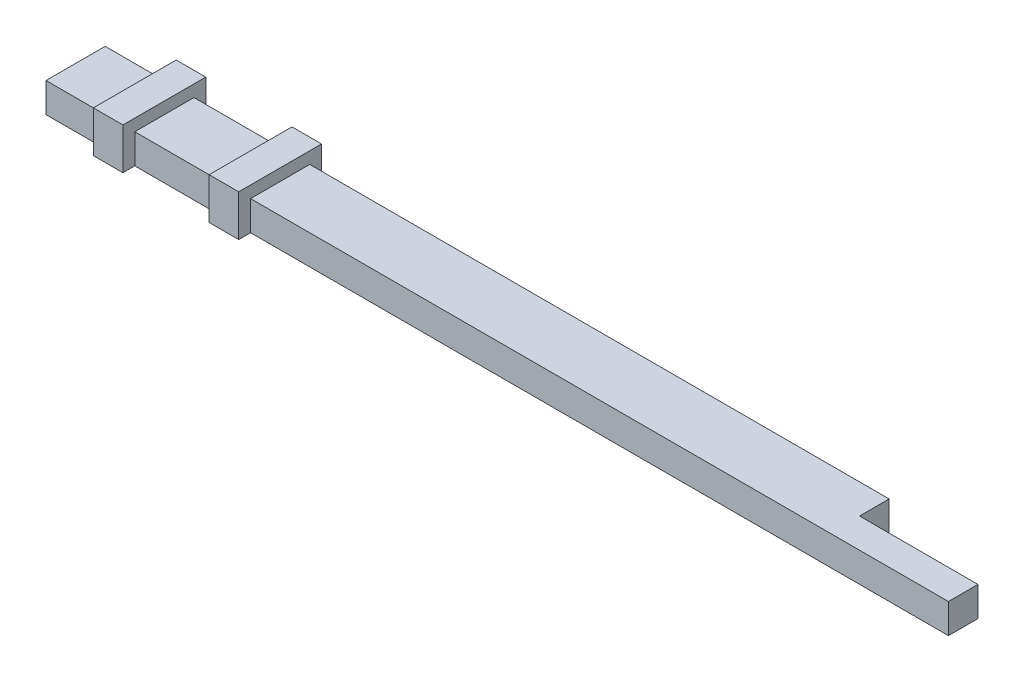
SolidWorks part; units mm, degrees
ref_plane "Front Plane" through (0, 0, 0) normal (0, 0, 1) x (1, 0, 0)
ref_plane "Top Plane" through (0, 0, 0) normal (0, 1, 0) x (1, 0, 0)
ref_plane "Right Plane" through (0, 0, 0) normal (1, 0, 0) x (0, 0, -1)
sketch "Sketch1" plane through (0, 0, 0) normal (0, 1, 0) x (1, 0, 0)
  line L0 (132.4815, 10) -> (132.4815, 5)
  line L1 (0, 0) -> (142.5, 0)
  line L2 (0, 0) -> (0, 10)
  line L3 (0, 10) -> (132.4815, 10)
  line L5 (142.5, 0) -> (152.5, 0)
  line L7 (142.4815, 5) -> (152.5, 5)
  line L8 (152.5, 0) -> (152.5, 5)
  line L9 (132.4815, 5) -> (142.4815, 5)
  dimension "D1" = 142.5
  dimension "D2" = 10
  dimension "D3" = 10
  dimension "D4" = 10
extrude "Boss-Extrude1" add sketch "Sketch1" along normal blind 5
ref_plane "Plane1" through (10, 0, 0) normal (-1, 0, 0) x (0, 0, 1)
sketch "Sketch2" plane through (10, 0, 0) normal (-1, 0, 0) x (0, 0, 1)
  line L0 (-10, 5) -> (0, 5) construction
  line L1 (-12, 7) -> (2, 7)
  line L2 (-12, 7) -> (-12, 0)
  line L3 (-12, 0) -> (2, 0)
  line L4 (2, 7) -> (2, 0)
  line L5 (-10, 0) -> (0, 0) construction
  line L6 (0, 5) -> (0, 0) construction
  line L7 (-10, 5) -> (-10, 0) construction
  dimension "D1" = 2
  dimension "D2" = 0
  dimension "D3" = 2
  dimension "D4" = 2
extrude "Boss-Extrude2" add sketch "Sketch2" against normal blind 5
ref_plane "Plane2" through (34.57, 0, 0) normal (1, 0, 0) x (0, 0, -1)
sketch "Sketch3" plane through (34.57, 0, 0) normal (1, 0, 0) x (0, 0, -1)
  line L1 (-2, 7) -> (12, 7)
  line L2 (-2, 7) -> (-2, 0)
  line L3 (-2, 0) -> (12, 0)
  line L4 (12, 7) -> (12, 0)
extrude "Boss-Extrude3" add sketch "Sketch3" against normal blind 5
